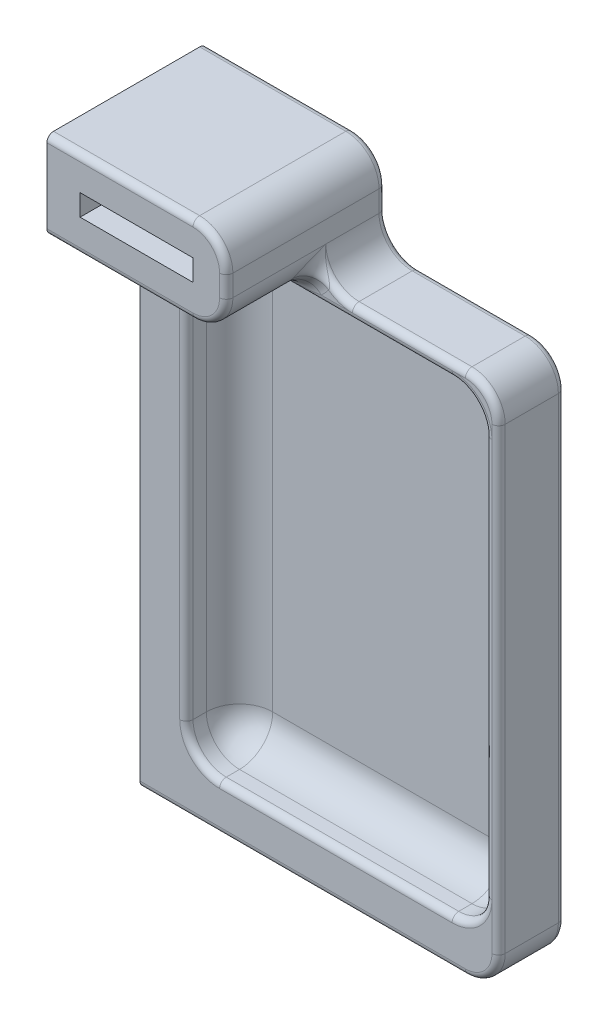
SolidWorks part; units mm, degrees
ref_plane "Piano frontale" through (0, 0, 0) normal (0, 0, 1) x (1, 0, 0)
ref_plane "Piano superiore" through (0, 0, 0) normal (0, 1, 0) x (1, 0, 0)
ref_plane "Piano destro" through (0, 0, 0) normal (1, 0, 0) x (0, 0, -1)
sketch "Schizzo1" plane through (0, 0, 0) normal (0, 0, 1) x (1, 0, 0)
  line L0 (-2, -2) -> (47, -2) construction
  line L1 (0, 0) -> (45, 0) construction
  line L2 (0, 0) -> (0, 70) construction
  line L3 (0, 70) -> (45, 70) construction
  line L4 (45, 0) -> (45, 70) construction
  line L5 (47, -2) -> (47, 72)
  line L6 (-2, 72) -> (47, 72)
  line L7 (-2, -2) -> (-2, 72) construction
  line L8 (-2, 72) -> (-7, 72)
  line L9 (-2, -2) -> (47, -2) construction
  line L10 (-2, -2) -> (-2, -7) construction
  line L11 (-2, -7) -> (47, -7)
  line L12 (47, -2) -> (47, -7)
  line L13 (-7, 72) -> (-7, -7)
  line L14 (-7, -7) -> (-2, -7)
  dimension "D1" = 45
  dimension "D2" = 70
  dimension "D4" = 5
  dimension "D5" = 5
  dimension "D3" = 2
extrude "Estrusione-Estrusione1" add sketch "Schizzo1" along normal blind 10
sketch "Schizzo2" plane through (0, 0, 10) normal (0, 0, 1) x (1, 0, 0)
  line L0 (0, 0) -> (45, 0)
  line L1 (-7, -7) -> (47, -7) construction
  line L8 (0, 72) -> (0, -7)
  line L9 (0, 70) -> (0, 0)
  line L10 (-5, 70) -> (-5, -5)
  line L11 (-5, 70) -> (-5, -5) construction
  line L13 (-5, -5) -> (45, -5)
  line L14 (45, -5) -> (45, 70)
  line L15 (45, 70) -> (-5, 70)
  line L18 (45, 0) -> (45, 70)
  line L19 (45, 70) -> (0, 70)
  line L20 (-5, -5) -> (45, -5) construction
  dimension "D2" = 7
  dimension "D1" = 2
  dimension "D3" = 7
extrude "Taglio-Estrusione1" cut sketch "Schizzo2" against normal blind 8
fillet "Raccordo1" radius 5 10 edges at (47, 72, 5) (45, 35, 2) (45, 70, 6) (22.5, 70, 2) (47, -7, 5) (45, 0, 6) (22.5, 0, 2) (0, 0, 6) (0, 70, 6) (0, 35, 2)
sketch "Schizzo3" plane through (0, 0, 0) normal (0, 0, -1) x (-1, 0, 0)
  line L5 (-15, 77) -> (2, 77) construction
  line L6 (-15, 77) -> (-15, 80.2) construction
  line L7 (-15, 80.2) -> (2, 80.2) construction
  line L8 (2, 77) -> (2, 80.2) construction
  line L9 (-15, 77) -> (2, 80.2) construction
  line L10 (-15, 80.2) -> (2, 77) construction
  line L13 (-20, 85.2) -> (7, 85.2)
  line L14 (-20, 85.2) -> (-20, 72)
  line L15 (-20, 72) -> (7, 72)
  line L16 (7, 85.2) -> (7, 72)
  line L17 (-20, 85.2) -> (7, 72) construction
  line L18 (-20, 72) -> (7, 85.2) construction
  point P0 (-6.5, 78.6)
  point P9 (-6.5, 78.6)
  dimension "D1" = 3.2
  dimension "D2" = 17
  dimension "D3" = 5
  dimension "D4" = 5
extrude "Estrusione-Estrusione2" add sketch "Schizzo3" against normal blind 24
sketch "Schizzo4" plane through (0, 0, 24) normal (0, 0, 1) x (1, 0, 0)
  line L0 (20, 85.2) -> (-7, 72) construction
  line L1 (-7, 85.2) -> (-7, -7) construction
  line L2 (-2, 80.2) -> (15, 80.2)
  line L3 (-2, 80.2) -> (-2, 77)
  line L4 (-2, 77) -> (15, 77)
  line L5 (15, 80.2) -> (15, 77)
  line L6 (-2, 80.2) -> (15, 77) construction
  line L7 (-2, 77) -> (15, 80.2) construction
  point P4 (6.5, 78.6)
  dimension "D1" = 3.2
  dimension "D2" = 17
extrude "Taglio-Estrusione2" cut sketch "Schizzo4" against normal blind 22
fillet "Raccordo3" radius 5 2 edges at (20, 85.2, 12) (20, 72, 17)
fillet "Raccordo4" radius 5 1 edges at (20, 72, 5)
sketch "Schizzo5" plane through (0, -7, 0) normal (0, -1, 0) x (-1, 0, 0)
  line L0 (-22.5, 0) -> (-22.5, -10) construction
  line L3 (-12.5, -5) -> (-32.5, -5) construction
  circle A0 centre (-12.5, -5) radius 2.4
  circle A1 centre (-32.5, -5) radius 2.4
  point P8 (-22.5, -5)
  point P9 (-22.5, -5)
  dimension "D1" = 4.8
  dimension "D2" = 20
  dimension "D3" = 24.5
extrude "Taglio-Estrusione3" cut sketch "Schizzo5" against normal blind 5
sketch "Schizzo6" plane through (-7, 0, 0) normal (-1, 0, 0) x (0, 0, 1)
  line L0 (24, 78.6) -> (0, 78.6) construction
  line L1 (24, 72) -> (24, 85.2) construction
  line L2 (0, 85.2) -> (0, -7) construction
  line L3 (5, -7) -> (5, 78.6) construction
  line L4 (10, -7) -> (0, -7) construction
  line L5 (24, 85.2) -> (0, 85.2) construction
  circle A0 centre (5, 8) radius 2.4
  circle A1 centre (5, 70.2) radius 2.4
  circle A2 centre (19, 78.6) radius 2.4
  dimension "D1" = 4.8
  dimension "D2" = 15
  dimension "D3" = 15
  dimension "D4" = 5
extrude "Taglio-Estrusione4" cut sketch "Schizzo6" against normal blind 5.5
fillet "Raccordo6" radius 1 28 edges at (21.4645, 73.4645, 10) (33.5, 72, 10) (45.5355, 70.5355, 10) (47, 32.5, 10) (45.5355, -5.5355, 10) (17.5, -7, 10) (22.5, 70, 10) (43.5355, 68.5355, 10) (45, 35, 10) (43.5355, 1.4645, 10) (22.5, 0, 10) (1.4645, 1.4645, 10) (0, 35, 10) (1.4645, 68.5355, 10) (4, 85.2, 0) (18.5355, 83.7355, 24) (18.5355, 83.7355, 0) (20, 78.6, 0) (21.4645, 73.4645, 0) (33.5, 72, 0) (45.5355, 70.5355, 0) (47, 32.5, 0) (45.5355, -5.5355, 0) (17.5, -7, 0) (4, 85.2, 24) (20, 78.6, 24) (18.5355, 73.4645, 24) (4, 72, 24)
fillet "Raccordo7" radius 3 3 edges at (19.7074, 75.3146, 9.8953) (17.6078, 72.7339, 10) (4, 72, 10)
sketch "Schizzo8" plane through (0, 0, 2) normal (0, 0, 1) x (1, 0, 0)
  line L0 (15, 80.2) -> (-2, 80.2) construction
  line L2 (4, 81.7) -> (9, 81.7)
  line L3 (4, 81.7) -> (4, 78.7)
  line L4 (4, 78.7) -> (9, 78.7)
  line L5 (9, 81.7) -> (9, 78.7)
  line L6 (4, 81.7) -> (9, 78.7) construction
  line L7 (4, 78.7) -> (9, 81.7) construction
  point P0 (6.5, 80.2)
  dimension "D1" = 3
  dimension "D2" = 5
extrude "Taglio-Estrusione6" cut sketch "Schizzo8" against normal blind 10 and the other way blind 14
sketch "Schizzo9" plane through (0, 0, 0) normal (0, 0, -1) x (-1, 0, 0)
  line L0 (7, 84.2) -> (7, -6) construction
  line L1 (-6.5, 78.7) -> (7, 78.7)
  line L2 (-6.5, 78.7) -> (-6.5, 81.7)
  line L3 (-6.5, 81.7) -> (7, 81.7)
  line L4 (7, 78.7) -> (7, 81.7)
  line L5 (-4, 81.7) -> (-9, 81.7) construction
  line L6 (-9, 78.7) -> (-4, 78.7) construction
extrude "Taglio-Estrusione7" cut sketch "Schizzo9" against normal blind 3
fillet "Raccordo8" radius 0.75 10 edges at (9, 80.2, 9) (4, 80.2, 9.5) (9, 78.7, 1) (9, 81.7, 8) (4, 81.7, 9.5) (-1.5, 81.7, 3) (-4.5, 78.7, 3) (-2, 79.45, 3) (1, 80.2, 3) (-2, 78.7, 2.5)
equation "\"D5@Schizzo1\"=\"D4@Schizzo1\""
